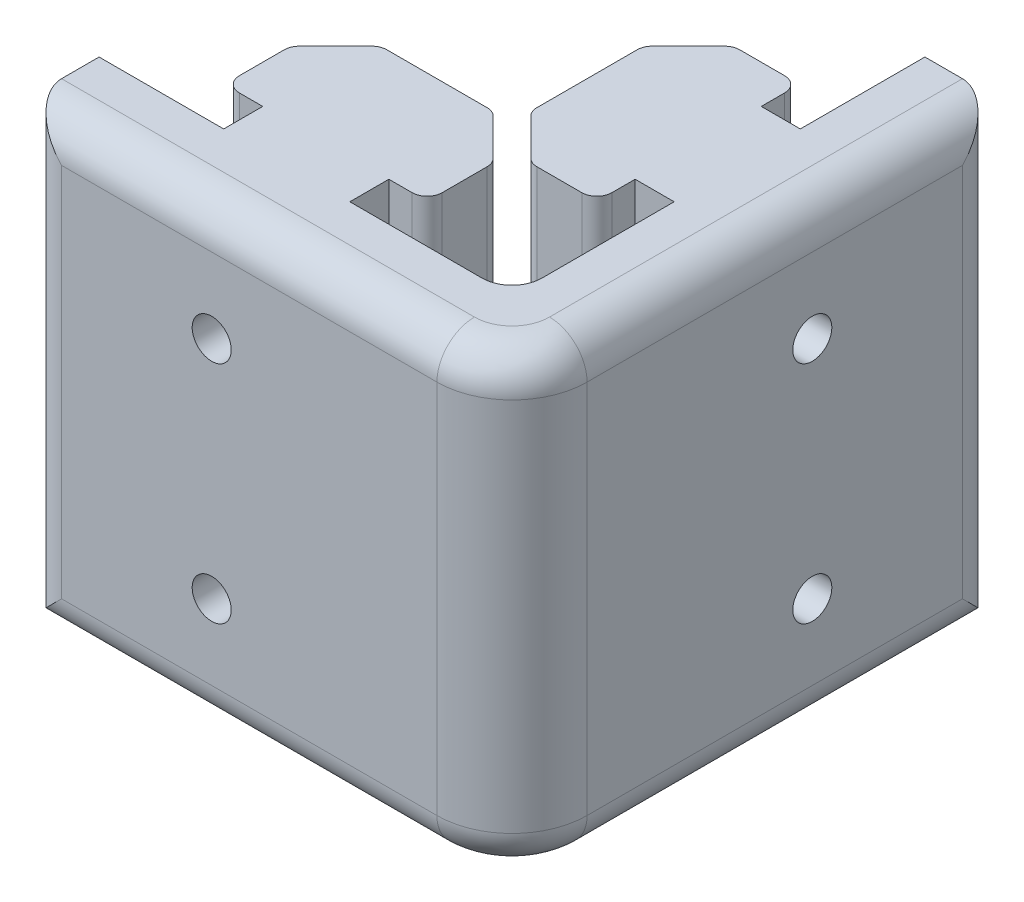
SolidWorks part; units mm, degrees
ref_plane "Front Plane" through (0, 0, 0) normal (0, 0, 1) x (1, 0, 0)
ref_plane "Top Plane" through (0, 0, 0) normal (0, 1, 0) x (1, 0, 0)
ref_plane "Right Plane" through (0, 0, 0) normal (1, 0, 0) x (0, 0, -1)
sketch "Sketch1" plane through (0, 0, 0) normal (0, 1, 0) x (1, 0, 0)
  line L0 (20, 20) -> (20, -20)
  line L1 (15, 15) -> (-15, 15)
  line L2 (15, 15) -> (15, -15)
  line L3 (15, -15) -> (-15, -15)
  line L4 (-15, 15) -> (-15, -15)
  line L5 (15, 15) -> (-15, -15) construction
  line L6 (15, -15) -> (-15, 15) construction
  line L7 (20, -20) -> (-20, -20)
  line L8 (-20, 20) -> (-20, -20)
  line L9 (20, 20) -> (-20, 20)
  line L10 (-15, -15) -> (-15, -20)
  line L11 (15, 15) -> (20, 15)
  line L12 (-15, 0) -> (15, 0) construction
  line L13 (0, 15) -> (0, -15) construction
  line L14 (-6.75, -8) -> (-3.75, -5)
  line L15 (-4.2, -12.4) -> (4.2, -12.4)
  line L16 (-4.2, -12.4) -> (-4.2, -15)
  line L17 (-4.2, -15) -> (4.2, -15)
  line L18 (4.2, -12.4) -> (4.2, -15)
  line L19 (-4.2, -12.4) -> (4.2, -15) construction
  line L20 (-4.2, -15) -> (4.2, -12.4) construction
  line L21 (-6.75, -8) -> (6.75, -8)
  line L22 (-6.75, -8) -> (-6.75, -12.4)
  line L23 (-6.75, -12.4) -> (6.75, -12.4)
  line L24 (6.75, -8) -> (6.75, -12.4)
  line L25 (-6.75, -8) -> (6.75, -12.4) construction
  line L26 (-6.75, -12.4) -> (6.75, -8) construction
  line L27 (-3.75, -5) -> (3.75, -5)
  line L28 (-3.75, -5) -> (-3.75, -8)
  line L29 (-3.75, -8) -> (3.75, -8)
  line L30 (3.75, -5) -> (3.75, -8)
  line L31 (-3.75, -5) -> (3.75, -8) construction
  line L32 (-3.75, -8) -> (3.75, -5) construction
  line L33 (3.75, -5) -> (6.75, -8)
  line L34 (12.4, -4.2) -> (15, -4.2)
  line L35 (12.4, 4.2) -> (15, 4.2)
  line L36 (8, 6.75) -> (5, 3.75)
  line L37 (5, 3.75) -> (5, -3.75)
  line L38 (5, -3.75) -> (8, -6.75)
  line L39 (8, 6.75) -> (12.4, 6.75)
  line L40 (12.4, 6.75) -> (12.4, -6.75)
  line L41 (8, -6.75) -> (12.4, -6.75)
  circle A0 centre (15, -15) radius 5
  point P0 (0, 0)
  point P16 (0, -13.7)
  point P21 (0, -10.2)
  point P26 (0, -6.5)
  dimension "D1" = 30
  dimension "D3" = 8.4
  dimension "D4" = 2.6
  dimension "D5" = 13.5
  dimension "D6" = 4.4
  dimension "D7" = 7.5
  dimension "D8" = 10
  dimension "D2" = 5
extrude "Boss-Extrude1" add sketch "Sketch1" along normal blind 30 contours A0 L3 L10 L7 | A0 L2 L3 | A0 L0 L11 L2 | L35 L40 L34 L2 | L38 L41 L40 L39 L36 L37 | L18 L15 L16 L3 | L24 L21 L22 L23 L15 | L28 L14 L21 | L30 L27 L28 L21 | L33 L30 L21 region at (17.5569, 0, -1.9396) region at (15.7074, 0, 15.7074) region at (-1.9396, 0, 17.5569) region at (13.7, 0, 0) region at (8.9673, 0, 0) region at (0, 0, 13.7) region at (0, 0, 10.2) region at (4.75, 0, 7) region at (-4.75, 0, 7) region at (0, 0, 6.5)
sketch "Sketch2" plane through (0, 0, 20) normal (0, 0, 1) x (1, 0, 0)
  line L0 (0, 0) -> (0, 30) construction
  line L1 (15, 30) -> (-15, 30) construction
  line L2 (-15, 15) -> (15, 15) construction
  line L3 (-15, 30) -> (-15, 0) construction
  line L4 (15, 30) -> (15, 0) construction
  circle A0 centre (0, 22.5) radius 1.3
  circle A1 centre (0, 7.5) radius 1.3
  dimension "D1" = 2.6
  dimension "D2" = 15
extrude "Cut-Extrude1" cut sketch "Sketch2" against normal up to next
sketch "Sketch3" plane through (20, 0, 0) normal (1, 0, 0) x (0, 0, -1)
  line L0 (0, 0) -> (0, 30) construction
  line L1 (15, 30) -> (-15, 30) construction
  line L2 (15, 15) -> (-15, 15) construction
  line L3 (15, 30) -> (15, 0) construction
  line L4 (-15, 30) -> (-15, 0) construction
  circle A0 centre (0, 22.5) radius 1.3
  circle A1 centre (0, 7.5) radius 1.3
  dimension "D1" = 2.6
  dimension "D2" = 15
extrude "Cut-Extrude2" cut sketch "Sketch3" against normal up to next
sketch "Sketch4" plane through (0, 0, 20) normal (0, 0, 1) x (1, 0, 0)
  line L0 (15, 0) -> (-15, 0) construction
  line L1 (-15, 30) -> (-12.5, 30)
  line L2 (-15, 30) -> (-15, 0)
  line L3 (-15, 0) -> (-12.5, 0)
  line L4 (-12.5, 30) -> (-12.5, 0)
  dimension "D1" = 2.5
extrude "Cut-Extrude3" cut sketch "Sketch4" against normal up to next
sketch "Sketch5" plane through (20, 0, 0) normal (1, 0, 0) x (0, 0, -1)
  line L0 (15, 0) -> (-15, 0) construction
  line L1 (15, 30) -> (12.5, 30)
  line L2 (15, 30) -> (15, 0)
  line L3 (15, 0) -> (12.5, 0)
  line L4 (12.5, 30) -> (12.5, 0)
  dimension "D1" = 2.5
extrude "Cut-Extrude4" cut sketch "Sketch5" against normal up to next
fillet "Fillet1" radius 2.5 8 edges at (1.25, 0, 20) (20, 0, 1.25) (1.25, 30, 20) (20, 30, 1.25) (18.5355, 0, 18.5355) (18.5355, 30, 18.5355) (20, 15, -12.5) (-12.5, 15, 20)
fillet "Fillet2" radius 2 1 edges at (15, 15, 15)
fillet "Fillet3" radius 1 12 edges at (12.4, 15, -6.75) (8, 15, -6.75) (5, 15, -3.75) (5, 15, 3.75) (8, 15, 6.75) (12.4, 15, 6.75) (6.75, 15, 12.4) (-6.75, 15, 12.4) (-3.75, 15, 5) (-6.75, 15, 8) (3.75, 15, 5) (6.75, 15, 8)
